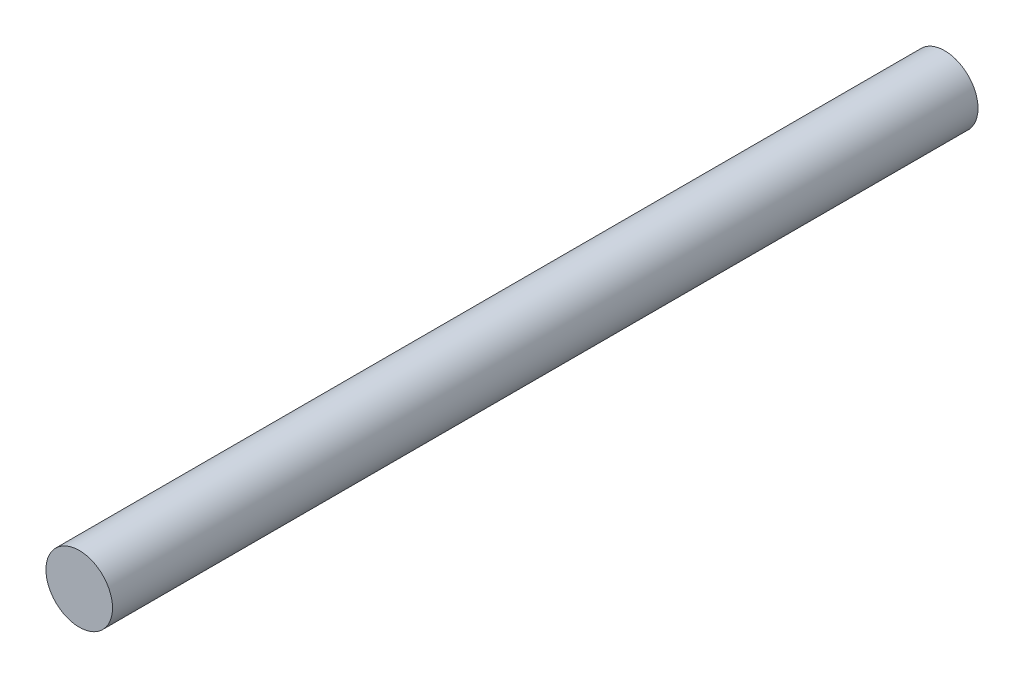
SolidWorks part; units mm, degrees
material "AISI 1010 Steel, hot rolled bar"
ref_plane "Front Plane" through (0, 0, 0) normal (0, 0, 1) x (1, 0, 0)
ref_plane "Top Plane" through (0, 0, 0) normal (0, 1, 0) x (1, 0, 0)
ref_plane "Right Plane" through (0, 0, 0) normal (1, 0, 0) x (0, 0, -1)
sketch "Sketch2" plane through (0, 0, 0) normal (0, 0, 1) x (1, 0, 0)
  circle A0 centre (0, 0) radius 6.35
  dimension "D1" = 12.7
extrude "Boss-Extrude1" add sketch "Sketch2" along normal blind 165.1
